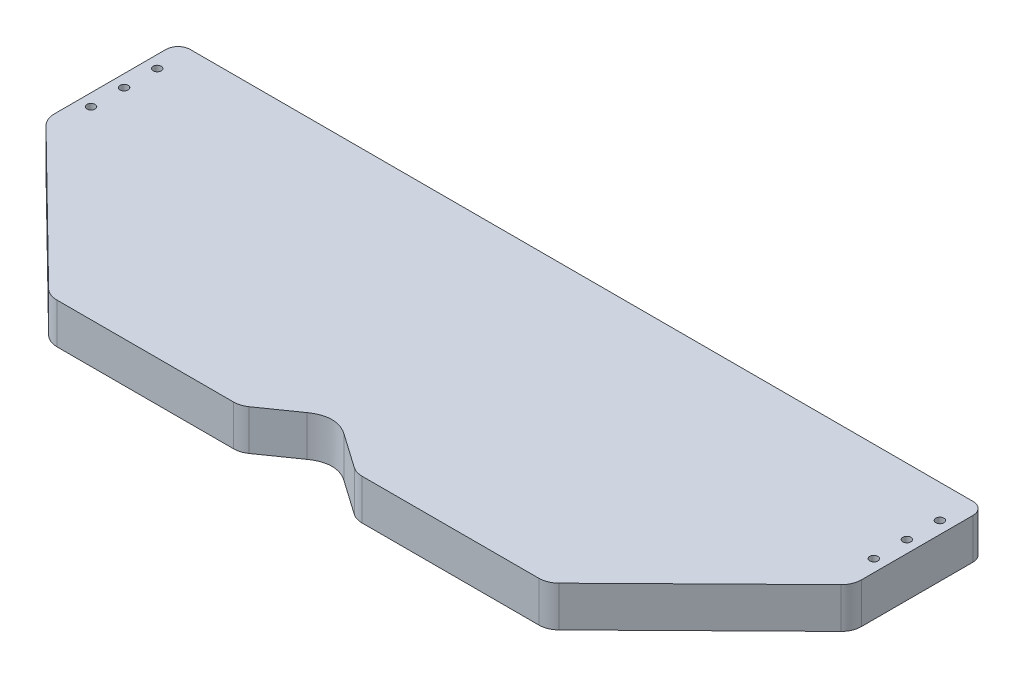
SolidWorks part; units mm, degrees
ref_plane "Front Plane" through (0, 0, 0) normal (0, 0, 1) x (1, 0, 0)
ref_plane "Top Plane" through (0, 0, 0) normal (0, 1, 0) x (1, 0, 0)
ref_plane "Right Plane" through (0, 0, 0) normal (1, 0, 0) x (0, 0, -1)
sketch "Sketch1" plane through (0, 0, 0) normal (0, 1, 0) x (1, 0, 0)
  line L0 (0, -60) -> (-14.2815, -70)
  line L1 (-14.2815, -70) -> (-61.5015, -70)
  line L2 (-61.5015, -70) -> (-99.58, -32.62)
  line L3 (-99.58, -32.62) -> (-99.58, 0)
  line L4 (-99.58, 0) -> (99.58, 0)
  line L5 (99.58, 0) -> (99.58, -32.62)
  line L6 (99.58, -32.62) -> (61.5015, -70)
  line L7 (61.5015, -70) -> (14.2815, -70)
  line L8 (14.2815, -70) -> (0, -60)
  line L9 (0, -38.5) -> (0, 38.5) construction
  circle A0 centre (96.58, -8.16) radius 1
  circle A1 centre (96.58, -16.32) radius 1
  circle A2 centre (96.58, -24.48) radius 1
  circle A3 centre (-96.58, -24.48) radius 1
  circle A4 centre (-96.58, -16.32) radius 1
  circle A5 centre (-96.58, -8.16) radius 1
  point P10 (0, 0)
  dimension "D7" = 3
  dimension "D8" = 2
  dimension "D1" = 70
  dimension "D2" = 10
  dimension "D3" = 35
  dimension "D4" = 199.16
  dimension "D5" = 123.003
  dimension "D9" = 8.16
  dimension "D11" = 8.16
  dimension "D12" = 32.62
  dimension "D10" = 3
extrude "Boss-Extrude1" add sketch "Sketch1" along normal mid plane 10
fillet "Fillet1" radius 5 2 edges at (14.2815, 0, 70) (-14.2815, 0, 70)
fillet "Fillet2" radius 5 2 edges at (-61.5015, 0, 70) (61.5015, 0, 70)
fillet "Fillet3" radius 5 2 edges at (-99.58, 0, 32.62) (99.58, 0, 32.62)
fillet "Fillet4" radius 3 2 edges at (99.58, 0, 0) (-99.58, 0, 0)
fillet "Fillet5" radius 8 1 edges at (0, 0, 60) conic rho 0.5
